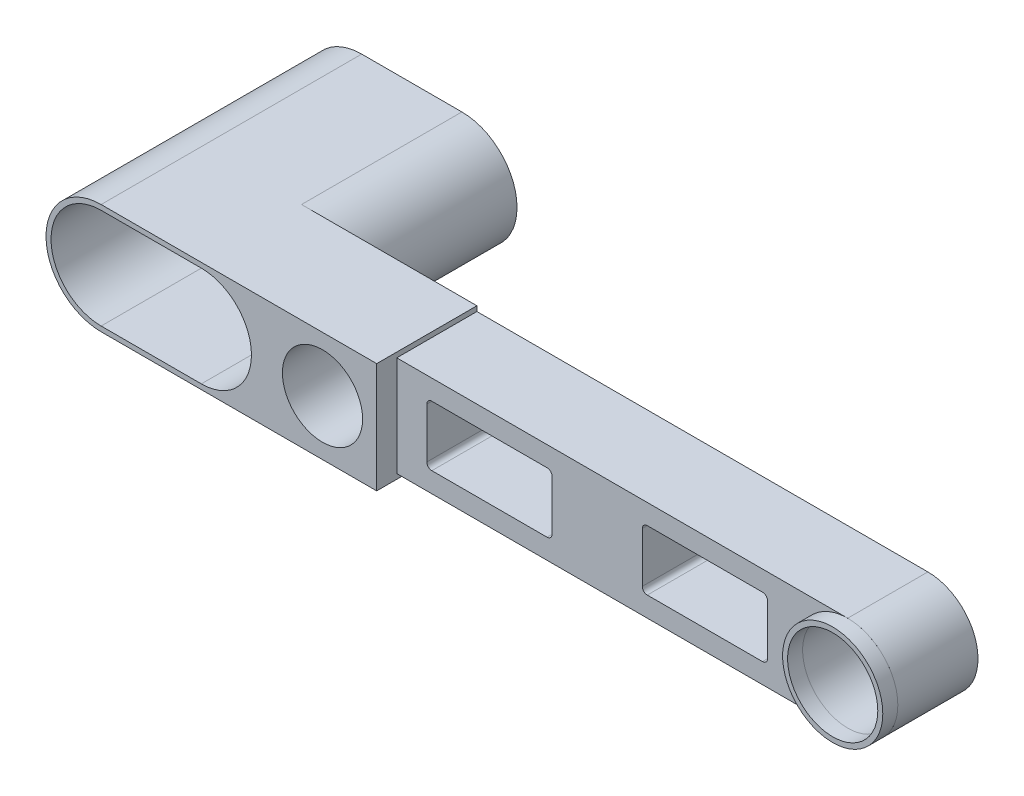
SolidWorks part; units mm, degrees
material "Cast Stainless Steel"
ref_plane "Front Plane" through (0, 0, 0) normal (0, 0, 1) x (1, 0, 0)
ref_plane "Top Plane" through (0, 0, 0) normal (0, 1, 0) x (1, 0, 0)
ref_plane "Right Plane" through (0, 0, 0) normal (1, 0, 0) x (0, 0, -1)
other "Center of Mass"
sketch "Sketch1" plane through (0, 0, 0) normal (1, 0, 0) x (0, 0, -1)
  line L0 (0, 0) -> (-500, 0) construction
  line L5 (-500, 50) -> (-50, 50)
  line L6 (50, -55) -> (-50, -55)
  line L7 (50, -55) -> (50, 55)
  line L8 (50, 55) -> (-50, 55)
  line L9 (-50, -55) -> (-50, 55)
  line L10 (50, -55) -> (-50, 55) construction
  line L11 (50, 55) -> (-50, -55) construction
  line L12 (-500, -50) -> (-50, -50)
  line L13 (0, 0) -> (280, 0)
  line L15 (280, 0) -> (50, 0)
  line L16 (280, 0) -> (280, 55)
  line L17 (280, 55) -> (50, 55)
  line L18 (50, 0) -> (50, 55)
  line L19 (280, 0) -> (50, 0)
  line L20 (280, 0) -> (280, -55)
  line L21 (280, -55) -> (50, -55)
  line L22 (50, 0) -> (50, -55)
  circle A0 centre (-500, 0) radius 50
  dimension "D1" = 100
  dimension "D2" = 110
  dimension "D3" = 100
  dimension "D4" = 500
  dimension "D5" = 280
extrude "Boss-Extrude1" add sketch "Sketch1" along normal blind 100 contours A0 L9 | A0 | L9 L6 L7 L8 | L21 L20 L13 L7 | L16 L17 L7 L13 region at (0, 0, 255.5167) region at (0, 0, 500) region at (0, 52.5, 48.5134) region at (0, 27.5, -165) region at (0, -27.5, -165)
sketch "Sketch2" plane through (0, 55, 0) normal (0, 1, 0) x (1, 0, 0)
  line L0 (0, 280) -> (260, 280)
  line L1 (260, 280) -> (260, 70)
  line L2 (260, 70) -> (100, 70)
  line L4 (0, 280) -> (0, -50)
  line L5 (0, -50) -> (100, -50)
  line L6 (100, -50) -> (100, 280)
  line L7 (100, 280) -> (0, 280)
  line L8 (0, 280) -> (0, -50)
  line L10 (100, -50) -> (100, 280)
  line L11 (100, 280) -> (0, 280)
  line L15 (0, -50) -> (100, -50)
  line M9 (100, -50) -> (100, 280)
  dimension "D2" = 260
  dimension "D3" = 210
  dimension "D1" = 0
extrude "Boss-Extrude2" add sketch "Sketch2" against normal up to surface (110 mm away) contours L2 L1 L0 M9 region at (180, 55, -175)
sketch "Sketch3" plane through (260, 0, 0) normal (1, 0, 0) x (0, 0, -1)
  line L4 (70, -55) -> (280, -55)
  line L5 (280, -55) -> (280, 55)
  line L6 (280, 55) -> (70, 55)
  line L7 (70, 55) -> (70, -55)
  line L8 (70, -55) -> (280, -55)
  line L9 (280, -55) -> (280, 55)
  line L10 (280, 55) -> (70, 55)
  line L11 (70, 55) -> (70, -55)
  circle A0 centre (125, 0) radius 55
  circle A1 centre (225, 0) radius 55
  line M5 (70, -55) -> (280, -55)
  line M6 (280, -55) -> (280, 55)
  line M7 (280, 55) -> (70, 55)
  line M8 (70, 55) -> (70, -55)
  dimension "D1" = 0
extrude "Cut-Extrude1" cut sketch "Sketch3" against normal up to surface (260 mm away) contours A1 L9 M7 | A1 M5 M6 region at (260, -42.7148, -267.7148) region at (260, 42.7148, -267.7148) up to face at (0, 0, 86.25)
extrude "Cut-Extrude2" cut sketch "Sketch3<3>" against normal up to surface (160 mm away) contours A0 L10 M8 | A0 L11 M5 region at (260, -42.7148, -82.2852) region at (260, 42.7148, -82.2852) up to face at (100, 0, 138.75)
sketch "Sketch3<3>" plane through (260, 0, 0) normal (1, 0, 0) x (0, 0, -1) same geometry as "Sketch3"
ref_plane "Plane1" through (-27.37, 0, 0) normal (-1, 0, 0) x (0, 0, 1)
sketch "Sketch12" plane through (0, 0, 0) normal (-1, 0, 0) x (0, 0, 1)
  line L0 (500, 0) -> (-225, 0) construction
  line L1 (85, 30) -> (200, 30)
  line L2 (80, 25) -> (80, -25)
  line L3 (85, -30) -> (200, -30)
  line L4 (205, 25) -> (205, -25)
  line L5 (250, 30) -> (250, -35.6293) construction
  line L6 (-225, -55) -> (50, -55)
  line L7 (50, -55) -> (50, -50)
  line L8 (50, -50) -> (500, -50)
  line L9 (500, 50) -> (50, 50)
  line L10 (50, 50) -> (50, 55)
  line L11 (50, 55) -> (-225, 55)
  line L12 (-225, -55) -> (50, -55)
  line L13 (50, -55) -> (50, -50)
  line L14 (50, -50) -> (500, -50)
  line L15 (500, 50) -> (50, 50)
  line L16 (50, 50) -> (50, 55)
  line L17 (50, 55) -> (-225, 55)
  line L22 (415, -30) -> (300, -30)
  line L23 (420, 25) -> (420, -25)
  line L24 (295, 25) -> (295, -25)
  line L25 (415, 30) -> (300, 30)
  arc A0 (415, 30) -> (420, 25) centre (415, 25) cw
  arc A1 (415, -30) -> (420, -25) centre (415, -25) ccw
  arc A2 (-225, 55) -> (-225, -55) centre (-225, 0) ccw
  arc A3 (500, -50) -> (500, 50) centre (500, 0) ccw
  arc A4 (-225, 55) -> (-225, -55) centre (-225, 0) ccw
  arc A5 (500, -50) -> (500, 50) centre (500, 0) ccw
  arc A6 (295, 25) -> (300, 30) centre (300, 25) cw
  arc A7 (295, -25) -> (300, -30) centre (300, -25) ccw
  arc A8 (205, 25) -> (200, 30) centre (200, 25) ccw
  arc A9 (205, -25) -> (200, -30) centre (200, -25) cw
  arc A10 (85, 30) -> (80, 25) centre (85, 25) ccw
  arc A11 (80, -25) -> (85, -30) centre (85, -25) ccw
  point P22 (420, 30)
  point P25 (420, -30)
  point P28 (295, 30)
  point P31 (295, -30)
  point P36 (205, 30)
  point P39 (205, -30)
  point P42 (80, 30)
  point P45 (80, -30)
  dimension "D6" = 5
  dimension "D2" = 125
  dimension "D3" = 60
  dimension "D4" = 80
  dimension "D5" = 45
  dimension "D1" = 0
extrude "Cut-Extrude3" cut sketch "Sketch12" against normal up to surface (100 mm away) contours L4 L1 L2 L3 | L23 L25 L24 L22 region at (0, 0, 142.5) region at (0, 0, 357.5) up to face at (100, 0, 131.875)
sketch "Sketch13" plane through (100, 0, 0) normal (1, 0, 0) x (0, 0, -1)
  line L0 (-50, -48) -> (125, -48)
  line L1 (125, -48) -> (225, -48)
  line L2 (125, -55) -> (225, -55)
  line L3 (225, 55) -> (125, 55)
  line L4 (125, -55) -> (225, -55)
  line L5 (225, 55) -> (125, 55)
  line L6 (-50, -55) -> (125, -55)
  line L7 (125, 55) -> (-50, 55)
  line L8 (-50, 55) -> (-50, 50)
  line L9 (-50, 50) -> (-500, 50)
  line L10 (-500, -50) -> (-50, -50)
  line L11 (-50, -50) -> (-50, -55)
  line L12 (-50, -55) -> (125, -55)
  line L13 (125, 55) -> (-50, 55)
  line L14 (-50, 55) -> (-50, 50)
  line L15 (-50, 50) -> (-500, 50)
  line L16 (-500, -50) -> (-50, -50)
  line L17 (-50, -50) -> (-50, -55)
  line L18 (225, 48) -> (125, 48)
  line L19 (125, 48) -> (-50, 48)
  line L20 (-43, 55) -> (-43, 50)
  line L21 (-50, 43) -> (-500, 43)
  line L22 (-50, -55) -> (225, -55)
  line L23 (-50, -50) -> (-50, -55)
  line L24 (-500, -50) -> (-50, -50)
  line L25 (-50, 50) -> (-500, 50)
  line L26 (-50, 55) -> (-50, 50)
  line L27 (225, 55) -> (-50, 55)
  line L28 (-50, -55) -> (225, -55)
  line L29 (-50, -50) -> (-50, -55)
  line L30 (-500, -50) -> (-50, -50)
  line L31 (-50, 50) -> (-500, 50)
  line L32 (-50, 55) -> (-50, 50)
  line L33 (225, 55) -> (-50, 55)
  line L34 (-500, -43) -> (-50, -43)
  line L35 (-43, -50) -> (-43, -55)
  line L36 (-50, -48) -> (225, -48)
  line L37 (225, 48) -> (-50, 48)
  line L38 (-43, -50) -> (-43, -55)
  line L39 (-500, -43) -> (-50, -43)
  line L40 (-50, 43) -> (-500, 43)
  line L41 (-43, 55) -> (-43, 50)
  line L42 (-50, -48) -> (-50, -43)
  line L43 (-50, 43) -> (-50, 48)
  arc A0 (225, -48) -> (225, 48) centre (225, 0) ccw
  arc A1 (225, -48) -> (225, 48) centre (225, 0) ccw
  arc A2 (125, 55) -> (125, -55) centre (125, 0) ccw
  arc A3 (-500, 50) -> (-500, -50) centre (-500, 0) ccw
  arc A5 (-500, 50) -> (-500, -50) centre (-500, 0) ccw
  arc A6 (125, 55) -> (125, -55) centre (125, 0) ccw
  arc A7 (225, -55) -> (225, 55) centre (225, 0) ccw
  arc A8 (-500, 43) -> (-500, -43) centre (-500, 0) ccw
  arc A9 (225, -55) -> (225, 55) centre (225, 0) ccw
  arc A10 (225, -55) -> (225, 55) centre (225, 0) ccw
  arc A11 (-500, 50) -> (-500, -50) centre (-500, 0) ccw
  arc A12 (225, -55) -> (225, 55) centre (225, 0) ccw
  arc A13 (-500, 50) -> (-500, -50) centre (-500, 0) ccw
  arc A14 (-500, 43) -> (-500, -43) centre (-500, 0) ccw
  dimension "D1" = 0
  dimension "D2" = 0
  dimension "D3" = 0
  dimension "D4" = 7
move or copy body "Body-Move/Copy1" bodies to move or copy 113 copy no rotation origin (130, 0, 135) rotation axis (0, 1, 0) rotation angle 86
sketch "Sketch15" plane through (-17.83, 0, 254.9802) normal (-0.0698, 0, 0.9976) x (0.9976, 0, 0.0698)
  line L6 (-220.8995, -55) -> (54.1005, -55)
  line L7 (54.1005, -55) -> (54.1005, -50)
  line L8 (54.1005, -50) -> (504.1005, -50)
  line L9 (504.1005, 50) -> (54.1005, 50)
  line L10 (54.1005, 50) -> (54.1005, 55)
  line L11 (54.1005, 55) -> (-220.8995, 55)
  line L12 (-220.8995, -55) -> (54.1005, -55)
  line L13 (54.1005, -55) -> (54.1005, -50)
  line L14 (54.1005, -50) -> (504.1005, -50)
  line L15 (504.1005, 50) -> (54.1005, 50)
  line L16 (54.1005, 50) -> (54.1005, 55)
  line L17 (54.1005, 55) -> (-220.8995, 55)
  circle A0 centre (0, 0) radius 40
  arc A2 (-220.8995, 55) -> (-220.8995, -55) centre (-220.8995, 0) ccw
  arc A3 (504.1005, -50) -> (504.1005, 50) centre (504.1005, 0) ccw
  arc A4 (-220.8995, 55) -> (-220.8995, -55) centre (-220.8995, 0) ccw
  arc A5 (504.1005, -50) -> (504.1005, 50) centre (504.1005, 0) ccw
  point P0 (0, 0)
  dimension "D2" = 80
  dimension "D1" = 0
extrude "Cut-Extrude4" cut sketch "Sketch15" against normal blind 84 contours A0 region at (-17.83, 0, 254.9802)
sketch "Sketch16" plane through (-17.83, 0, 254.9802) normal (-0.0698, 0, 0.9976) x (0.9976, 0, 0.0698)
  point P0 (0, 0)
move or copy body "Body-Move/Copy2" bodies to move or copy 117 copy no translate (17.83, 0, -254.9802)
sketch "Sketch17" plane through (0, 0, 0) normal (-0.0698, 0, 0.9976) x (0.9976, 0, 0.0698)
  line L0 (54.1005, 50) -> (54.1005, -50)
  line L6 (-220.8995, -55) -> (54.1005, -55)
  line L7 (54.1005, -55) -> (54.1005, -50)
  line L8 (54.1005, -50) -> (504.1005, -50)
  line L9 (504.1005, 50) -> (54.1005, 50)
  line L10 (54.1005, 50) -> (54.1005, 55)
  line L11 (54.1005, 55) -> (-220.8995, 55)
  line L12 (-220.8995, -55) -> (54.1005, -55)
  line L13 (54.1005, -55) -> (54.1005, -50)
  line L14 (54.1005, -50) -> (504.1005, -50)
  line L15 (504.1005, 50) -> (54.1005, 50)
  line L16 (54.1005, 50) -> (54.1005, 55)
  line L17 (54.1005, 55) -> (-220.8995, 55)
  arc A2 (-220.8995, 55) -> (-220.8995, -55) centre (-220.8995, 0) ccw
  arc A3 (504.1005, -50) -> (504.1005, 50) centre (504.1005, 0) ccw
  arc A4 (-220.8995, 55) -> (-220.8995, -55) centre (-220.8995, 0) ccw
  arc A5 (504.1005, -50) -> (504.1005, 50) centre (504.1005, 0) ccw
  line M10 (204.1005, -30) -> (89.1005, -30)
  arc M11 (89.1005, -30) -> (84.1005, -25) centre (89.1005, -25) cw
  line M12 (84.1005, -25) -> (84.1005, 25)
  arc M13 (84.1005, 25) -> (89.1005, 30) centre (89.1005, 25) cw
  line M14 (89.1005, 30) -> (204.1005, 30)
  arc M15 (204.1005, 30) -> (209.1005, 25) centre (204.1005, 25) cw
  line M16 (209.1005, 25) -> (209.1005, -25)
  arc M17 (209.1005, -25) -> (204.1005, -30) centre (204.1005, -25) cw
  line M18 (419.1005, -30) -> (304.1005, -30)
  arc M19 (304.1005, -30) -> (299.1005, -25) centre (304.1005, -25) cw
  line M20 (299.1005, -25) -> (299.1005, 25)
  arc M21 (299.1005, 25) -> (304.1005, 30) centre (304.1005, 25) cw
  line M22 (304.1005, 30) -> (419.1005, 30)
  arc M23 (419.1005, 30) -> (424.1005, 25) centre (419.1005, 25) cw
  line M24 (424.1005, 25) -> (424.1005, -25)
  arc M25 (424.1005, -25) -> (419.1005, -30) centre (419.1005, -25) cw
  line M29 (54.1005, -50) -> (504.1005, -50)
  arc M30 (504.1005, -50) -> (504.1005, 50) centre (504.1005, 0) ccw
  line M31 (504.1005, 50) -> (54.1005, 50)
  dimension "D1" = 0
extrude "Cut-Extrude5" cut sketch "Sketch17" against normal blind 20 contours L0 M31 M29 M30 M25 M18 M19 M20 M21 M22 M23 M24 M17 M10 M11 M12 M13 M14 M15 M16 region at (278.4206, 44.901, 19.4691)
sketch "Sketch18" plane through (1.3951, 0, -19.9513) normal (-0.0698, 0, 0.9976) x (0.9976, 0, 0.0698)
  line L3 (504.1005, 50) -> (54.1005, 50)
  line L4 (54.1005, 50) -> (54.1005, -50)
  line L5 (54.1005, -50) -> (504.1005, -50)
  line L6 (504.1005, 50) -> (54.1005, 50)
  line L7 (54.1005, 50) -> (54.1005, -50)
  line L8 (54.1005, -50) -> (504.1005, -50)
  circle A0 centre (504.1005, 0) radius 50
  arc A1 (504.1005, -50) -> (504.1005, 50) centre (504.1005, 0) ccw
  arc A2 (504.1005, -50) -> (504.1005, 50) centre (504.1005, 0) ccw
  arc M24 (504.1005, -50) -> (504.1005, 50) centre (504.1005, 0) ccw
  dimension "D1" = 0
extrude "Boss-Extrude3" add sketch "Sketch18" along normal blind 15 separate body contours A0 M24 region at (504.2676, 0, 15.213)
move or copy body "Body-Move/Copy6" bodies to move or copy 119 120 copy no rotation origin (0, 0, 0) rotation axis (0, 1, 0) rotation angle 4
ref_plane "Plane2" through (0, 0, 27.37) normal (0, 0, 1) x (1, 0, 0)
ref_axis "Axis1" through (0, 0, -84) along (0, 0, 1)
ref_point "Point1"
move or copy body "Body-Move/Copy7" bodies to move or copy 127 128 copy no translate (0, 0, -27.37)
sketch "Sketch19" plane through (0, 0, -287.37) normal (0, 0, -1) x (-1, 0, 0)
  line L4 (120.8995, -50) -> (220.8995, -50)
  line L5 (220.8995, 50) -> (120.8995, 50)
  line L6 (120.8995, -50) -> (220.8995, -50)
  line L7 (220.8995, 50) -> (120.8995, 50)
  arc A4 (120.8995, 50) -> (120.8995, -50) centre (120.8995, 0) ccw
  arc A5 (220.8995, -50) -> (220.8995, 50) centre (220.8995, 0) ccw
  arc A6 (120.8995, 50) -> (120.8995, -50) centre (120.8995, 0) ccw
  arc A7 (220.8995, -50) -> (220.8995, 50) centre (220.8995, 0) ccw
  dimension "D1" = 5
extrude "Cut-Extrude6" cut sketch "Sketch19" against normal blind 270
sketch "Sketch20" plane through (0, 0, -32.37) normal (0, 0, 1) x (1, 0, 0)
  circle A2 centre (504.1005, 0) radius 45
  circle A3 centre (504.1005, 0) radius 45
  dimension "D1" = 5
extrude "Cut-Extrude7" cut sketch "Sketch20" against normal blind 70 contours A3
